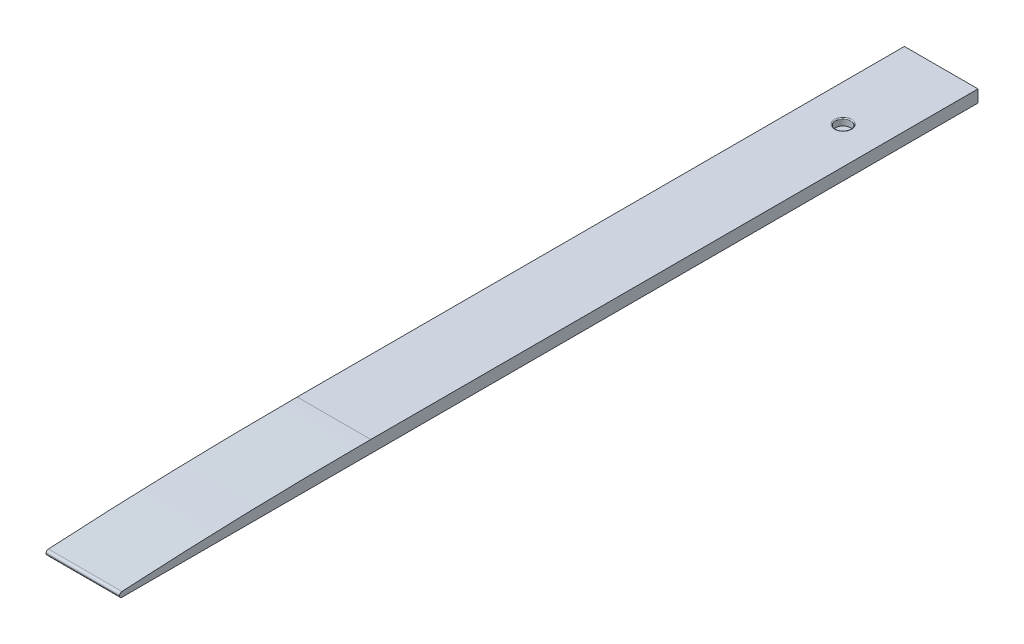
SolidWorks part; units mm, degrees
other "标注1"
sketch "草图6" plane through (0, 5, 350) normal (-0.6393, 0.5849, 0.4992) x (0.7619, 0.3939, 0.5141)
ref_plane "前视基准面" through (0, 0, 0) normal (0, 0, 1) x (1, 0, 0)
ref_plane "上视基准面" through (0, 0, 0) normal (0, 1, 0) x (1, 0, 0)
ref_plane "右视基准面" through (0, 0, 0) normal (1, 0, 0) x (0, 0, -1)
other "Configuration Table"
sketch "草图1" plane through (0, 0, 0) normal (1, 0, 0) x (0, 0, -1)
  line L0 (0, 0) -> (-350, 0)
  line L5 (0, 5) -> (0, 0)
  line L6 (-300, 5) -> (0, 5)
  line L7 (-350, 0) -> (-350, 2)
  line L8 (-350, 2) -> (-300, 5)
  dimension "D1" = 350
  dimension "D2" = 5
  dimension "D3" = 2
  dimension "D7" = 50
extrude "凸台-拉伸1" add sketch "草图1" along normal blind 30
fillet "圆角1" radius 1750 1 edges at (15, 5, 300)
sketch "草图4" plane through (0, 5, 0) normal (0, 1, 0) x (1, 0, 0)
  line L0 (15, 0) -> (15, -40) construction
  line L1 (30, 0) -> (0, 0) construction
  line L2 (15, 0) -> (15, -40) construction
  circle A0 centre (15, -40) radius 3.1
  dimension "D2" = 6.2
  dimension "D1" = 40
extrude "切除-拉伸3" cut sketch "草图4" against normal blind 2.8
fillet "圆角4" radius 0.4 1 edges at (15, 5, 43.1)
sketch "草图5" plane through (0, 0, 0) normal (0, 0, -1) x (-1, 0, 0)
  line L0 (0, 0) -> (0, 5) construction
  line L1 (-25, 3.5) -> (-5, 3.5)
  line L2 (-25, 3.5) -> (-25, 1.5)
  line L3 (-25, 1.5) -> (-5, 1.5)
  line L4 (-5, 3.5) -> (-5, 1.5)
  line L5 (-30, 0) -> (-30, 5) construction
  line L6 (-30, 5) -> (0, 5) construction
  line L7 (-30, 0) -> (0, 0) construction
  dimension "D1" = 5
  dimension "D2" = 5
  dimension "D3" = 1.5
  dimension "D4" = 1.5
extrude "切除-拉伸4" cut sketch "草图5" against normal blind 25
fillet "圆角5" radius 1 2 edges at (15, 0, 350) (15, 2, 350)
fillet "圆角6" radius 1 2 edges at (15, 1.5, 0) (15, 3.5, 0)
